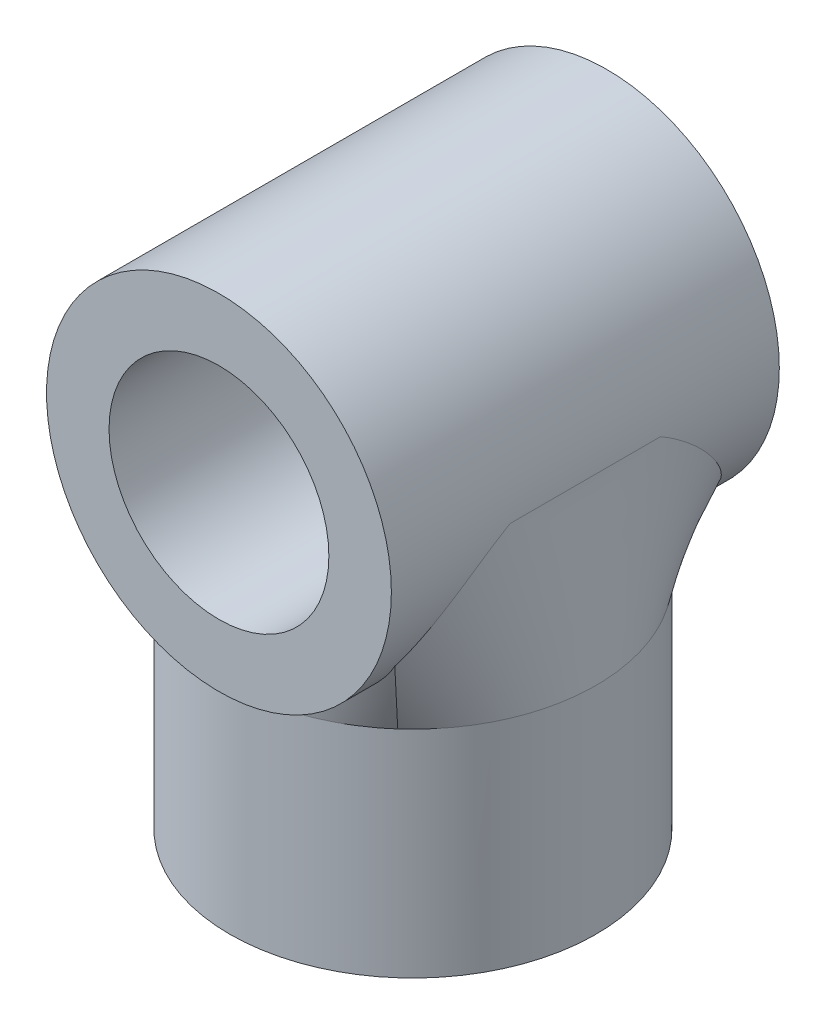
SolidWorks part; units mm, degrees
ref_plane "Front Plane" through (0, 0, 0) normal (0, 0, 1) x (1, 0, 0)
ref_plane "Top Plane" through (0, 0, 0) normal (0, 1, 0) x (1, 0, 0)
ref_plane "Right Plane" through (0, 0, 0) normal (1, 0, 0) x (0, 0, -1)
sketch "Sketch1" plane through (0, 0, 0) normal (0, 1, 0) x (1, 0, 0)
  circle A0 centre (0, 0) radius 6
  circle A1 centre (0, 0) radius 8.5
  dimension "D1" = 12
  dimension "D2" = 17
extrude "Boss-Extrude1" add sketch "Sketch1" along normal blind 10
sketch "Sketch3" plane through (0, 0, 0) normal (0, 0, 1) x (1, 0, 0)
  line L0 (8.5, 10) -> (-8.5, 10) construction
  circle A1 centre (0, 18) radius 8
  dimension "D2" = 16
extrude "Boss-Extrude2" add sketch "Sketch3" along normal blind 9 and the other way blind 9 separate body
ref_point "Point1"
ref_plane "Plane1" through (0, 18, 0) normal (0, 1, 0) x (1, 0, 0)
sketch "Sketch6" plane through (0, 10, 0) normal (0, 1, 0) x (1, 0, 0)
  circle A0 centre (0, 0) radius 8.5
  circle A1 centre (0, 0) radius 8.5 construction
sketch "Sketch7" plane through (0, 18, 0) normal (0, 1, 0) x (1, 0, 0)
  line L1 (-8, -9) -> (8, -9)
  line L2 (-8, -9) -> (-8, 9)
  line L3 (-8, 9) -> (8, 9)
  line L4 (8, -9) -> (8, 9)
  line L5 (-8, -9) -> (8, 9) construction
  line L6 (-8, 9) -> (8, -9) construction
  point P0 (0, 0)
loft "Loft1" add profiles "Sketch7", "Sketch6" connector at (-8, 18, -9) connector at (0, 10, 8.5)
sketch "Sketch8" plane through (0, 0, 9) normal (0, 0, 1) x (1, 0, 0)
  line L0 (9.35, 18) -> (-9.35, 18) construction
  circle A0 centre (0, 18) radius 5.1
  circle A1 centre (0, 18) radius 8 construction
  dimension "D1" = 10.2
extrude "Cut-Extrude1" cut sketch "Sketch8" against normal up to surface (18 mm away) up to face at (8, 18, -9)
equation "\"pin_bore\"=10.20"
equation "\"top_outer_diameter\"=16.00"
equation "\"D2@Sketch3\"=\"top_outer_diameter\""
equation "\"D1@Sketch8\"=\"pin_bore\""
equation "\"bottom_height\"=16.50"
equation "\"bottom_bore_height\"=8.50"
